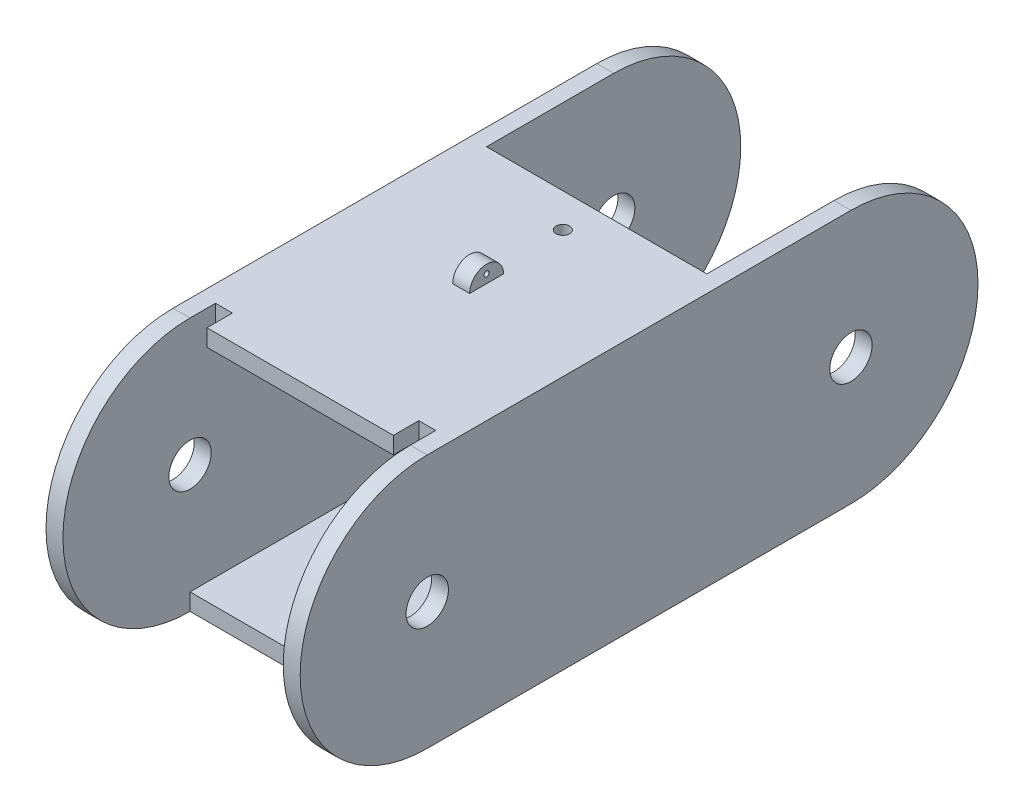
SolidWorks part; units mm, degrees
ref_plane "Front Plane" through (0, 0, 0) normal (0, 0, 1) x (1, 0, 0)
ref_plane "Top Plane" through (0, 0, 0) normal (0, 1, 0) x (1, 0, 0)
ref_plane "Right Plane" through (0, 0, 0) normal (1, 0, 0) x (0, 0, -1)
ref_plane "End Plane" through (0, 0, -31.75) normal (0, 0, 1) x (1, 0, 0)
ref_plane "Inside Plane" through (0, 19.05, 0) normal (0, 1, 0) x (1, 0, 0)
sketch "Sketch1" plane through (0, 0, 0) normal (0, 1, 0) x (1, 0, 0)
  line L1 (0, 0) -> (19.05, 0)
  line L2 (0, 0) -> (0, 50.8)
  line L3 (0, 50.8) -> (19.05, 50.8)
  line L4 (19.05, 0) -> (19.05, 50.8)
  dimension "D1" = 50.8
  dimension "D2" = 19.05
extrude "Boss-Extrude1" add sketch "Sketch1" along normal blind 19.05
sketch "Sketch2" plane through (0, 0, 0) normal (0, 0, 1) x (1, 0, 0)
  line L0 (0, 19.05) -> (19.05, 19.05) construction
  line L1 (1.27, 17.78) -> (17.78, 17.78)
  line L2 (1.27, 17.78) -> (1.27, 1.27)
  line L3 (1.27, 1.27) -> (17.78, 1.27)
  line L4 (17.78, 17.78) -> (17.78, 1.27)
  line L5 (0, 19.05) -> (0, 0) construction
  line L6 (0, 0) -> (19.05, 0) construction
  line L7 (19.05, 19.05) -> (19.05, 0) construction
  dimension "D1" = 1.27
  dimension "D2" = 1.27
  dimension "D3" = 1.27
  dimension "D4" = 1.27
extrude "Cut-Extrude1" cut sketch "Sketch2" against normal blind 50.8
sketch "Sketch3" plane through (0, 19.05, 0) normal (0, 1, 0) x (1, 0, 0)
  line L0 (0, 50.8) -> (0, 0) construction
  line L1 (8.89, 24.13) -> (10.16, 24.13)
  line L2 (8.89, 24.13) -> (8.89, 21.59)
  line L3 (8.89, 21.59) -> (10.16, 21.59)
  line L4 (10.16, 24.13) -> (10.16, 21.59)
  line L5 (0, 0) -> (19.05, 0) construction
  dimension "D1" = 1.27
  dimension "D2" = 8.89
  dimension "D3" = 21.59
  dimension "D4" = 2.54
extrude "Boss-Extrude2" add sketch "Sketch3" along normal blind 1.27
sketch "Sketch4" plane through (0, 0, 0) normal (1, 0, 0) x (0, 0, -1)
  line L0 (24.13, 19.05) -> (21.59, 19.05) construction
  line L1 (22.86, 20.32) -> (22.86, 19.685) construction
  line L2 (50.8, 19.05) -> (0, 19.05) construction
  line L3 (21.59, 20.32) -> (24.13, 20.32) construction
  line L4 (50.8, 0) -> (0, 0) construction
  line L5 (0, 19.05) -> (0, 0) construction
  circle A0 centre (22.86, 19.685) radius 0.1905
  arc A1 (24.13, 19.05) -> (21.59, 19.05) centre (22.86, 20.4483) ccw
  circle A4 centre (9.525, 9.525) radius 1.5875
  arc A6 (9.525, 19.05) -> (9.525, 0) centre (9.525, 9.525) ccw
  arc A7 (9.525, 19.05) -> (9.525, 0) centre (-8.7829, 9.525) ccw
  ellipse E0 centre (22.86, 19.05) end of major axis (22.86, 20.32) minor radius 1.27 (24.13, 19.05) -> (21.59, 19.05) ccw
  dimension "D1" = 0.635
  dimension "D4" = 9.525
  dimension "D5" = 9.525
extrude "Cut-Extrude2" cut sketch "Sketch4" along normal blind 19.05
fillet "Fillet1" [suppressed] radius 0.635
fillet "Fillet2" [suppressed] radius 2.54
ref_plane "Mirror Plane" through (0, 0, -25.4) normal (0, 0, 1) x (1, 0, 0)
mirror "Mirror1" about plane through (0, 0, -25.4) normal (0, 0, 1) of "Cut-Extrude2"
sketch "Sketch7" plane through (0, 19.05, 0) normal (0, 1, 0) x (1, 0, 0)
  line L0 (2.54, 9.525) -> (16.51, 9.525)
  line L1 (1.27, 0) -> (2.54, 0)
  line L2 (1.27, 0) -> (1.27, 11.43)
  line L3 (1.27, 11.43) -> (2.54, 11.43)
  line L4 (2.54, 9.525) -> (2.54, 11.43)
  line L5 (17.78, 0) -> (16.51, 0)
  line L6 (17.78, 0) -> (17.78, 11.43)
  line L7 (17.78, 11.43) -> (16.51, 11.43)
  line L8 (16.51, 9.525) -> (16.51, 11.43)
  line L9 (19.05, 9.525) -> (0, 9.525) construction
  line L10 (2.54, 0) -> (16.51, 0)
  line L11 (0, 41.275) -> (0, 9.525) construction
  line L13 (10.16, 24.13) -> (8.89, 24.13) construction
  circle A0 centre (9.525, 29.21) radius 0.508
  dimension "D5" = 9.525
  dimension "D1" = 1.27
  dimension "D2" = 1.27
  dimension "D3" = 11.43
  dimension "D4" = 11.43
  dimension "D6" = 5.08
extrude "Cut-Extrude3" cut sketch "Sketch7" against normal blind 12.7
sketch "Sketch8" plane through (0, 19.05, 0) normal (0, 1, 0) x (1, 0, 0)
  line L0 (1.27, 0) -> (1.27, 9.525) construction
  line L1 (1.27, 4.0341) -> (17.78, 4.0341)
  line L2 (1.27, 4.0341) -> (1.27, 9.525)
  line L3 (1.27, 9.525) -> (17.78, 9.525)
  line L4 (17.78, 4.0341) -> (17.78, 9.525)
extrude "Cut-Extrude4" cut sketch "Sketch8" against normal blind 25.4
sketch "Sketch9" plane through (0, 0, 0) normal (0, 1, 0) x (1, 0, 0)
  line L0 (1.27, 9.525) -> (17.78, 9.525) construction
  line L1 (12.065, 22.225) -> (8.255, 22.225)
  line L2 (12.065, 22.225) -> (12.065, 27.305)
  line L3 (12.065, 27.305) -> (8.255, 27.305)
  line L4 (8.255, 22.225) -> (8.255, 27.305)
  line L5 (19.05, 9.525) -> (19.05, 41.275) construction
  dimension "D1" = 3.81
  dimension "D2" = 5.08
  dimension "D3" = 12.7
  dimension "D4" = 6.985
extrude "Boss-Extrude3" [suppressed] add sketch "Sketch9" against normal blind 5.08
sketch "Sketch10" [suppressed] plane through (0, 0, 0) normal (1, 0, 0) x (0, 0, -1)
  line L0 (27.305, -5.08) -> (27.305, 0) construction
  line L1 (22.225, -5.08) -> (27.305, -5.08) construction
  line L2 (22.225, -5.08) -> (22.225, 0) construction
  line L3 (22.225, 0) -> (27.305, 0) construction
  line L4 (22.225, -2.54) -> (22.225, 0)
  line L5 (25.1652, 0) -> (27.305, 0)
  line L6 (9.525, 0) -> (41.275, 0) construction
  arc A0 (27.305, -2.54) -> (24.765, -5.08) centre (24.765, -2.54) cw
  arc A1 (24.765, -5.08) -> (22.225, -2.54) centre (24.765, -2.54) cw
  arc A2 (27.305, -2.54) -> (26.0285, -1.3339) centre (26.0637, -2.5752) ccw
  arc A3 (26.0285, -1.3339) -> (26.0483, -2.0347) centre (26.0384, -1.6843) ccw
  arc A4 (26.0483, -2.0347) -> (26.68, -2.5752) centre (26.0422, -2.6811) cw
  arc A5 (26.68, -2.5752) -> (24.765, -4.4612) centre (24.5539, -2.3316) cw
  arc A6 (24.765, -4.4612) -> (22.9012, -2.54) centre (25.0593, -2.311) cw
  arc A7 (22.9012, -2.54) -> (25.1652, 0) centre (27.0171, -3.9296) cw
  arc A8 (27.305, 0) -> (22.225, 0) centre (24.765, -2.8187) cw
extrude "Cut-Extrude5" [suppressed] cut sketch "Sketch10" along normal blind 25.4
sketch "Sketch11" plane through (0, 19.05, 0) normal (0, 1, 0) x (1, 0, 0)
  line L0 (19.05, 41.275) -> (0, 41.275) construction
  line L1 (1.27, 46.0269) -> (17.78, 46.0269)
  line L2 (1.27, 46.0269) -> (1.27, 31.75)
  line L3 (1.27, 31.75) -> (17.78, 31.75)
  line L4 (17.78, 46.0269) -> (17.78, 31.75)
  point P5 (0, 0)
  dimension "D1" = 9.525
extrude "Cut-Extrude6" cut sketch "Sketch11" against normal blind 2.54
sketch "Sketch12" plane through (0, 0, 0) normal (0, 1, 0) x (1, 0, 0)
  line L1 (1.27, 46.0269) -> (17.78, 46.0269)
  line L2 (1.27, 46.0269) -> (1.27, 41.275)
  line L3 (1.27, 41.275) -> (17.78, 41.275)
  line L4 (17.78, 46.0269) -> (17.78, 41.275)
extrude "Cut-Extrude7" cut sketch "Sketch12" along normal blind 2.54
